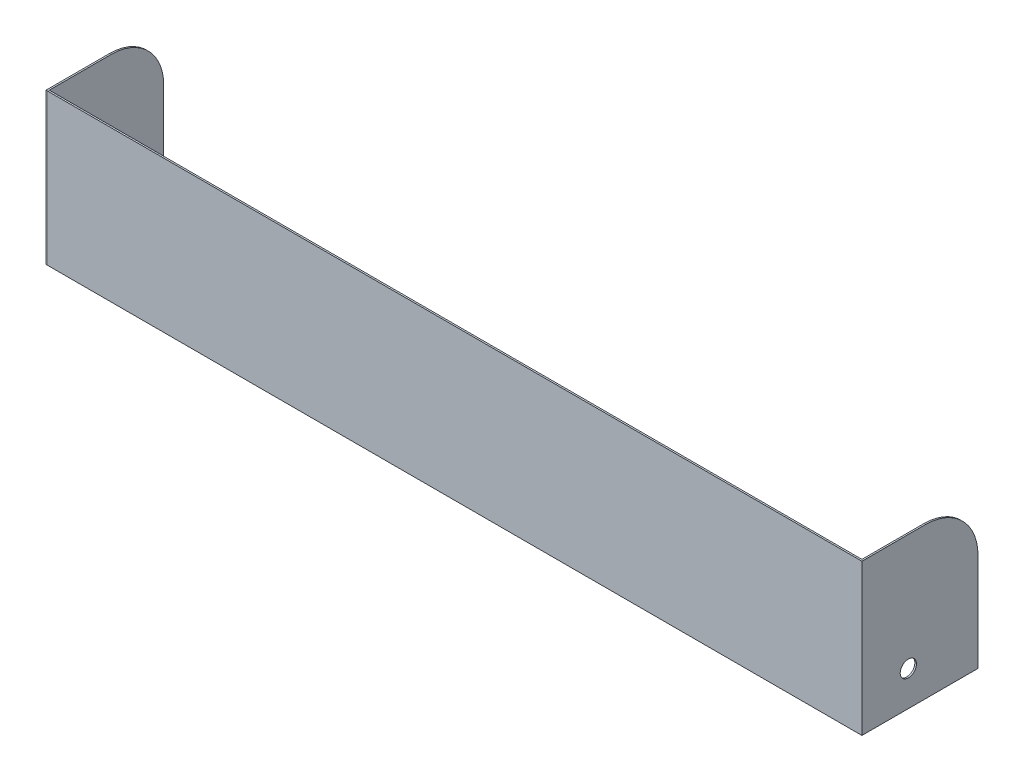
SolidWorks part; units mm, degrees
ref_plane "Front Plane" through (0, 0, 0) normal (0, 0, 1) x (1, 0, 0)
ref_plane "Top Plane" through (0, 0, 0) normal (0, 1, 0) x (1, 0, 0)
ref_plane "Right Plane" through (0, 0, 0) normal (1, 0, 0) x (0, 0, -1)
sketch "Sketch1" plane through (0, 0, 0) normal (0, 0, 1) x (1, 0, 0)
  line L0 (0, 283.3898) -> (0, -294.2373) construction
  line L1 (-518.8701, 0) -> (517.0621, 0) construction
  line L3 (-175, 32.5) -> (175, 32.5)
  line L4 (-175, 32.5) -> (-175, -32.5)
  line L5 (-175, -32.5) -> (175, -32.5)
  line L6 (175, 32.5) -> (175, -32.5)
  dimension "D1" = 350
  dimension "D2" = 65
extrude "Back Wall" add sketch "Sketch1" along normal blind 0.7
ref_plane "Right_wall Plane" through (-175, 0, 0) normal (-1, 0, 0) x (0, 0, 1)
sketch "Sketch2" plane through (-175, 0, 0) normal (-1, 0, 0) x (0, 0, 1)
  line L0 (-62.6179, 0) -> (70.933, 0) construction
  line L1 (0, 60.0387) -> (0, -42.0887) construction
  line L2 (0.7, -32.5) -> (-49.3, -32.5)
  line L3 (-49.3, -32.5) -> (-49.3, 9.6927)
  line L4 (0.7, 32.5) -> (0.7, -32.5) construction
  line L5 (0.7, 32.5) -> (-27.0019, 32.5)
  line L6 (0.7, 32.5) -> (0.7, -32.5)
  arc A0 (-49.3, 9.6927) -> (-27.0019, 32.5) centre (-26.4869, 9.6927) cw
  dimension "D2" = 22.8131
  dimension "D1" = 50
  dimension "D3" = 31.8963
extrude "Right Wall" add sketch "Sketch2" along normal blind 0.7 separate body
ref_plane "Left_wall Plane" through (175, 0, 0) normal (1, 0, 0) x (0, 0, -1)
ref_plane "Mid Plane" through (0, 0, 0) normal (1, 0, 0) x (0, 0, -1)
mirror "Mirror8" about plane through (0, 0, 0) normal (1, 0, 0) of "Right Wall"
sketch "Sketch6" plane through (-175, 0, 0) normal (-1, 0, 0) x (0, 0, 1)
  line L0 (0.7, -32.5) -> (0.7, 32.5) construction
  line L1 (-49.3, -32.5) -> (0.7, -32.5) construction
  circle A0 centre (-19.3, -17.5) radius 3.5
  dimension "D1" = 7
  dimension "D2" = 20
  dimension "D3" = 15
extrude "Cut-Extrude1" cut sketch "Sketch6" against normal through all both and the other way through all
